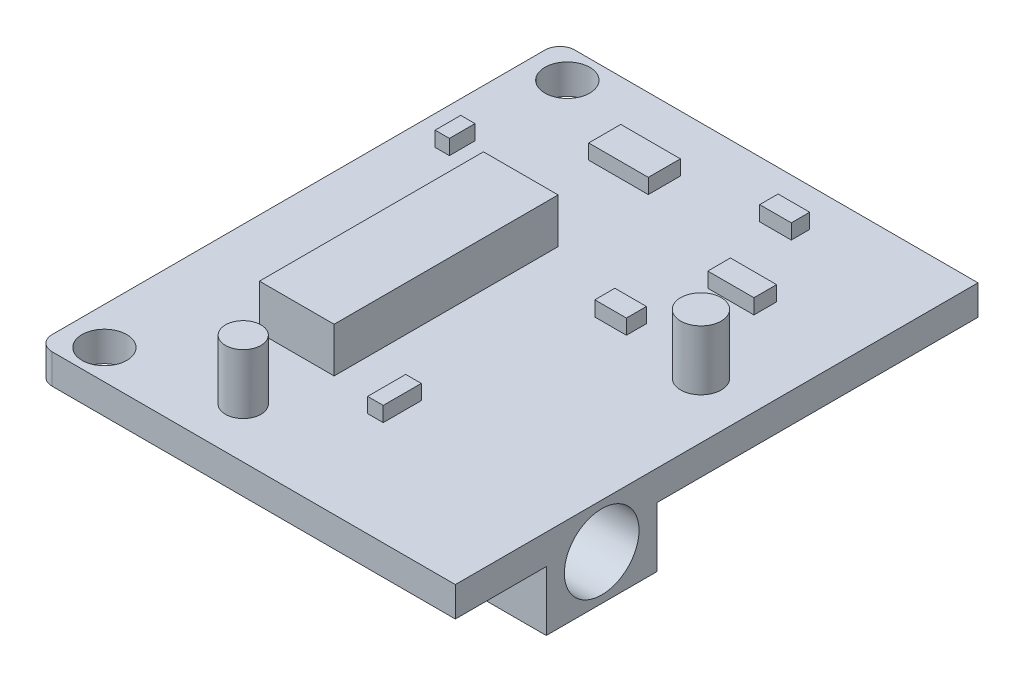
SolidWorks part; units mm, degrees
ref_plane "Front Plane" through (0, 0, 0) normal (0, 0, 1) x (1, 0, 0)
ref_plane "Top Plane" through (0, 0, 0) normal (0, 1, 0) x (1, 0, 0)
ref_plane "Right Plane" through (0, 0, 0) normal (1, 0, 0) x (0, 0, -1)
sketch "Sketch1" plane through (0, 0, 0) normal (0, 1, 0) x (1, 0, 0)
  line L1 (0, 0) -> (28, 0)
  line L2 (0, 0) -> (0, 35)
  line L3 (0, 35) -> (28, 35)
  line L4 (28, 0) -> (28, 35)
  line L5 (0, 0) -> (28, 35) construction
  line L6 (0, 35) -> (28, 0) construction
  circle A0 centre (2.5, 2) radius 1.5
  circle A1 centre (2.5, 33) radius 1.5
  point P4 (14, 17.5)
  dimension "D5" = 3
  dimension "D6" = 3
  dimension "D1" = 35
  dimension "D2" = 28
  dimension "D3" = 2
  dimension "D4" = 31
  dimension "D7" = 2.5
  dimension "D8" = 2.5
extrude "Boss-Extrude1" add sketch "Sketch1" along normal blind 2
sketch "Sketch2" plane through (0, 2, 0) normal (0, 1, 0) x (1, 0, 0)
  line L0 (28, 0) -> (28, 35) construction
  line L1 (28, 6.0888) -> (18.1965, 6.0888)
  line L2 (28, 6.0888) -> (28, 13.5)
  line L3 (28, 13.5) -> (18.1965, 13.5)
  line L4 (18.1965, 6.0888) -> (18.1965, 13.5)
  line L5 (28, 6.0888) -> (18.1965, 13.5) construction
  line L6 (28, 13.5) -> (18.1965, 6.0888) construction
  line L7 (28, 35) -> (0, 35) construction
  line L8 (7.8532, 29.0767) -> (11.844, 29.0767)
  line L9 (7.8532, 29.0767) -> (7.8532, 31.2258)
  line L10 (7.8532, 31.2258) -> (11.844, 31.2258)
  line L11 (11.844, 29.0767) -> (11.844, 31.2258)
  line L12 (7.8532, 29.0767) -> (11.844, 31.2258) construction
  line L13 (7.8532, 31.2258) -> (11.844, 29.0767) construction
  line L14 (17.1555, 31.2258) -> (19.2702, 31.2258)
  line L15 (17.1555, 31.2258) -> (17.1555, 32.4581)
  line L16 (17.1555, 32.4581) -> (19.2702, 32.4581)
  line L17 (19.2702, 31.2258) -> (19.2702, 32.4581)
  line L18 (17.1555, 31.2258) -> (19.2702, 32.4581) construction
  line L19 (17.1555, 32.4581) -> (19.2702, 31.2258) construction
  line L20 (6.844, 8.0386) -> (11.844, 8.0386)
  line L21 (6.844, 8.0386) -> (6.844, 23.0386)
  line L22 (6.844, 23.0386) -> (11.844, 23.0386)
  line L23 (11.844, 8.0386) -> (11.844, 23.0386)
  line L24 (6.844, 8.0386) -> (11.844, 23.0386) construction
  line L25 (6.844, 23.0386) -> (11.844, 8.0386) construction
  line L26 (19.2702, 25.6336) -> (22.3623, 25.6336)
  line L27 (19.2702, 25.6336) -> (19.2702, 27.1515)
  line L28 (19.2702, 27.1515) -> (22.3623, 27.1515)
  line L29 (22.3623, 25.6336) -> (22.3623, 27.1515)
  line L30 (19.2702, 25.6336) -> (22.3623, 27.1515) construction
  line L31 (19.2702, 27.1515) -> (22.3623, 25.6336) construction
  line L32 (19.2702, 20.1851) -> (17.1555, 20.1851)
  line L33 (19.2702, 20.1851) -> (19.2702, 21.5264)
  line L34 (19.2702, 21.5264) -> (17.1555, 21.5264)
  line L35 (17.1555, 20.1851) -> (17.1555, 21.5264)
  line L36 (19.2702, 20.1851) -> (17.1555, 21.5264) construction
  line L37 (19.2702, 21.5264) -> (17.1555, 20.1851) construction
  line L38 (15.1498, 6.9766) -> (16.1937, 6.9766)
  line L39 (15.1498, 6.9766) -> (15.1498, 9.5261)
  line L40 (15.1498, 9.5261) -> (16.1937, 9.5261)
  line L41 (16.1937, 6.9766) -> (16.1937, 9.5261)
  line L42 (15.1498, 6.9766) -> (16.1937, 9.5261) construction
  line L43 (15.1498, 9.5261) -> (16.1937, 6.9766) construction
  line L44 (1.9701, 24.6763) -> (2.9258, 24.6763)
  line L45 (1.9701, 24.6763) -> (1.9701, 26.3925)
  line L46 (1.9701, 26.3925) -> (2.9258, 26.3925)
  line L47 (2.9258, 24.6763) -> (2.9258, 26.3925)
  line L48 (1.9701, 24.6763) -> (2.9258, 26.3925) construction
  line L49 (1.9701, 26.3925) -> (2.9258, 24.6763) construction
  circle A0 centre (10.4327, 3.3631) radius 1.1888
  circle A1 centre (24.2622, 20.1851) radius 1.3583
  point P4 (23.0983, 9.7944)
  point P11 (9.8486, 30.1513)
  point P16 (18.2128, 31.8419)
  point P21 (9.344, 15.5386)
  point P26 (20.8163, 26.3925)
  point P31 (18.2128, 20.8558)
  point P36 (15.6717, 8.2513)
  point P41 (2.448, 25.5344)
  point P48 (0, 0)
  point P49 (0, 0)
  dimension "D1" = 9.8035
  dimension "D2" = 21.5
  dimension "D3" = 7.4112
  dimension "D4" = 5
  dimension "D5" = 15
extrude "Boss-Extrude2" add sketch "Sketch2" against normal blind 6 contours L4 L3 L2 L1
extrude "Boss-Extrude3" add sketch "Sketch2<3>" along normal blind 3 contours L22 L23 L20 L21
sketch "Sketch2<3>" plane through (0, 2, 0) normal (0, 1, 0) x (1, 0, 0) same geometry as "Sketch2"
extrude "Boss-Extrude4" add sketch "Sketch2<4>" along normal blind 4 contours A0 | A1
sketch "Sketch2<4>" plane through (0, 2, 0) normal (0, 1, 0) x (1, 0, 0) same geometry as "Sketch2"
extrude "Boss-Extrude5" add sketch "Sketch2<5>" along normal blind 1 contours L41 L40 L39 L38 | L34 L35 L32 L33 | L28 L29 L26 L27 | L16 L17 L14 L15 | L10 L11 L8 L9 | L45 L46 L47 L44
sketch "Sketch2<5>" plane through (0, 2, 0) normal (0, 1, 0) x (1, 0, 0) same geometry as "Sketch2"
fillet "Fillet1" radius 1 2 edges at (0, 1, 0) (0, 1, -35)
sketch "Sketch3" plane through (28, 0, 0) normal (1, 0, 0) x (0, 0, -1)
  line L0 (6.0888, -4) -> (13.5, -4) construction
  line L1 (13.5, -4) -> (13.5, 0) construction
  circle A0 centre (9.8, -1) radius 2.5
  dimension "D3" = 5
  dimension "D1" = 3
  dimension "D2" = 3.7
extrude "Cut-Extrude1" cut sketch "Sketch3" against normal blind 6
equation "\"D3@Sketch1\"=(\"D1@Sketch1\"-\"D4@Sketch1\")/2"
